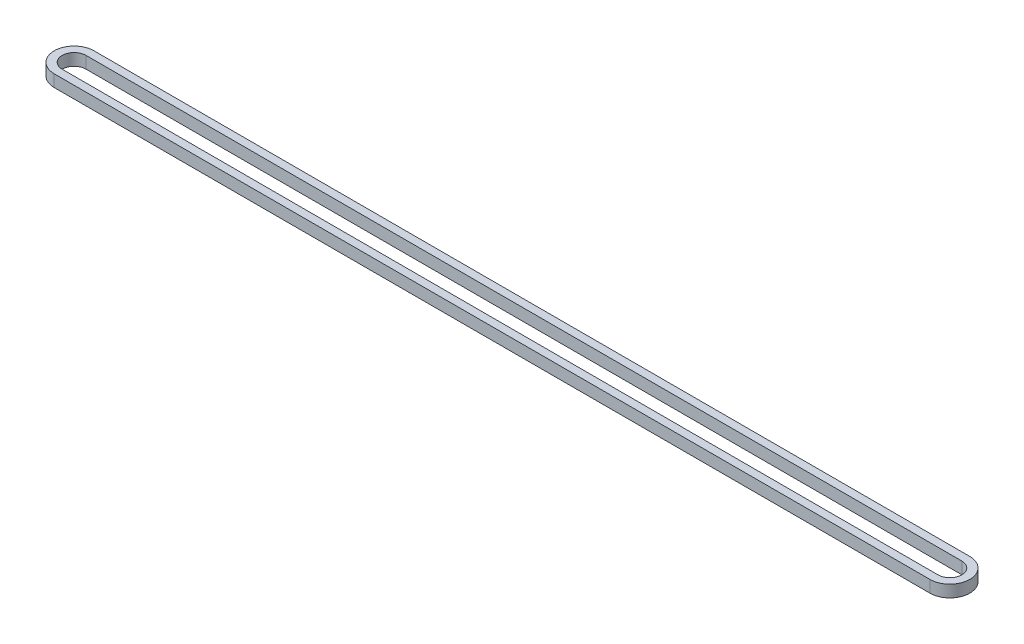
SolidWorks part; units mm, degrees
ref_plane "前视基准面" through (0, 0, 0) normal (0, 0, 1) x (1, 0, 0)
ref_plane "上视基准面" through (0, 0, 0) normal (0, 1, 0) x (1, 0, 0)
ref_plane "右视基准面" through (0, 0, 0) normal (1, 0, 0) x (0, 0, -1)
other "Configuration Table"
sketch "草图1" plane through (0, 0, 0) normal (0, 1, 0) x (1, 0, 0)
  line L0 (0, 0) -> (220, 0) construction
  line L1 (0, 3) -> (220, 3)
  line L2 (0, -3) -> (220, -3)
  arc A0 (0, 3) -> (0, -3) centre (0, 0) ccw
  arc A1 (220, -3) -> (220, 3) centre (220, 0) ccw
  point P3 (110, 0)
  dimension "D2" = 3
  dimension "D1" = 220
extrude "拉伸-薄壁1" add sketch "草图1" along normal blind 3 thin thin type one direction wall 2
